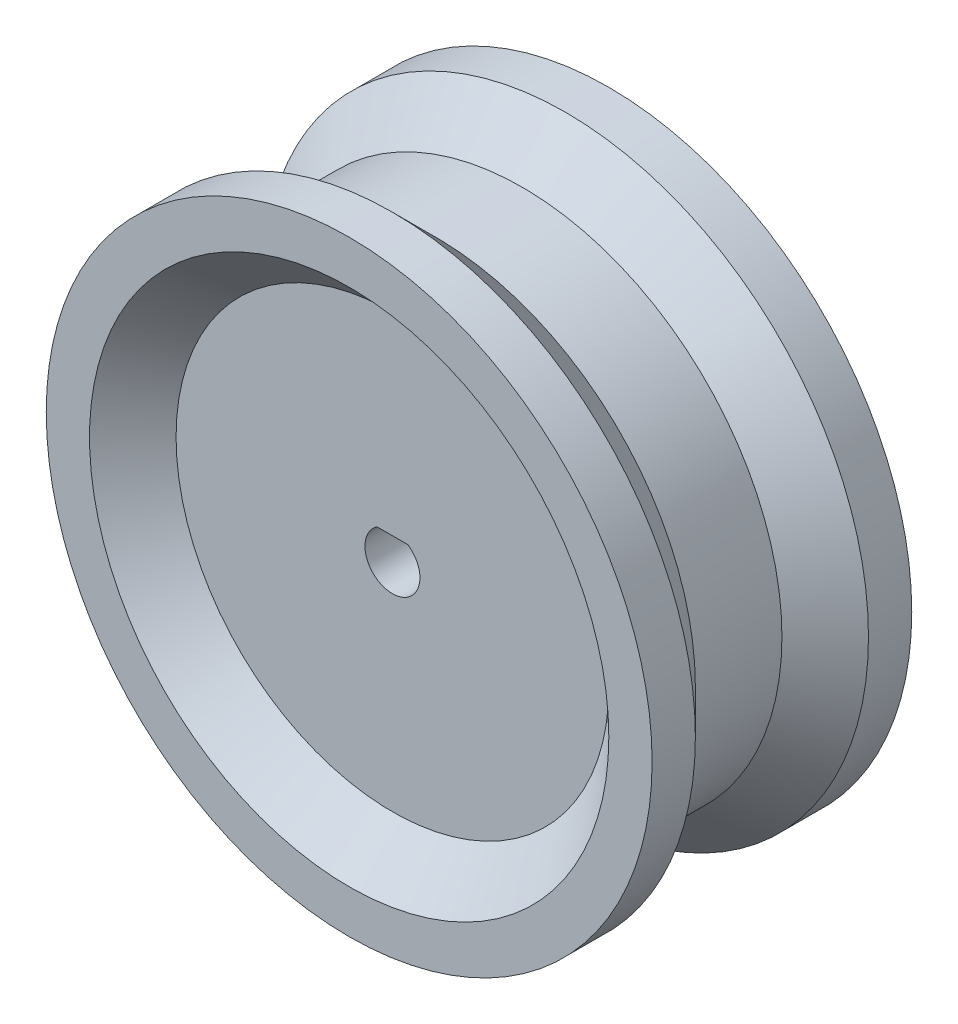
SolidWorks part; units mm, degrees
material "5052-H32"
ref_plane "Front Plane" through (0, 0, 0) normal (0, 0, 1) x (1, 0, 0)
ref_plane "Top Plane" through (0, 0, 0) normal (0, 1, 0) x (1, 0, 0)
ref_plane "Right Plane" through (0, 0, 0) normal (1, 0, 0) x (0, 0, -1)
sketch "Sketch1" plane through (0, 0, 0) normal (0, 0, 1) x (1, 0, 0)
  circle A0 centre (0, 0) radius 35
  dimension "D1" = 70
extrude "Boss-Extrude1" add sketch "Sketch1" along normal blind 30
sketch "Sketch3" plane through (0, 0, 30) normal (0, 0, 1) x (1, 0, 0)
  circle A0 centre (0, 0) radius 25
  dimension "D1" = 50
extrude "Cut-Extrude1" cut sketch "Sketch3" against normal blind 5
sketch "Sketch4" plane through (0, 0, 0) normal (0, 0, -1) x (-1, 0, 0)
  circle A0 centre (0, 0) radius 25
  dimension "D1" = 50
extrude "Cut-Extrude2" cut sketch "Sketch4" against normal blind 5
sketch "Sketch5" plane through (0, 0, 0) normal (1, 0, 0) x (0, 0, -1)
  line L0 (-25, 35) -> (-20, 30)
  line L1 (-20, 30) -> (-10, 30)
  line L2 (-10, 30) -> (-5, 35)
  line L3 (-5, 35) -> (-25, 35)
  line L4 (-30, 35) -> (-30, -35) construction
  line L6 (0, 35) -> (-30, 35) construction
  line L7 (-49.7677, 0) -> (30.7711, 0) construction
  point P2 (-9.4983, 0)
  dimension "D1" = 10
  dimension "D2" = 10
  dimension "D3" = 30
  dimension "D4" = 20
  dimension "D5" = 5
revolve "Cut-Revolve1" cut sketch "Sketch5" angle 360 about L7
sketch "Sketch6" plane through (0, 0, 25) normal (0, 0, 1) x (1, 0, 0)
  line L0 (-1.7861, 2.625) -> (1.7861, 2.625)
  arc A0 (-1.7861, 2.625) -> (1.7861, 2.625) centre (0, 0) ccw
  dimension "D1" = 6.35
  dimension "D2" = 2.625
extrude "Cut-Extrude3" cut sketch "Sketch6" against normal blind 39
chamfer "Chamfer2" distance 5 angle 45 2 edges at (-25, 0, 0) (25, 0, 30)
